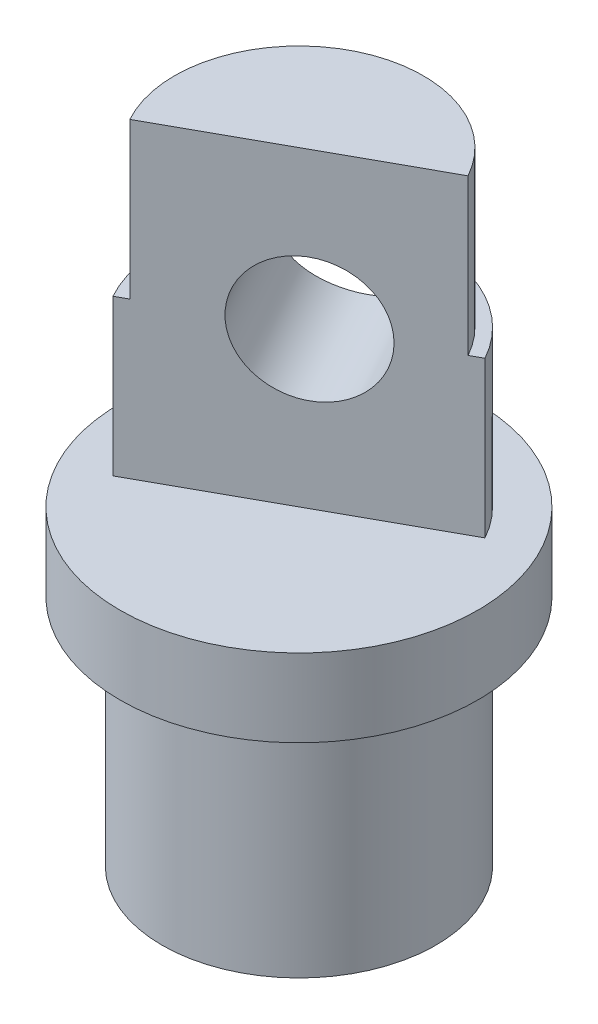
SolidWorks part; units mm, degrees
note: The reader was unsure of these and kept them because the rebuilt part matched: shared geometry of "Sketch1<4>", "Sketch1<6>", "Sketch1<7>", "Sketch1<8>", "Sketch1<10>".
ref_plane "Front Plane" through (0, 0, 0) normal (0, 0, 1) x (1, 0, 0)
ref_plane "Top Plane" through (0, 0, 0) normal (0, 1, 0) x (1, 0, 0)
ref_plane "Right Plane" through (0, 0, 0) normal (1, 0, 0) x (0, 0, -1)
sketch "Sketch1" plane through (0, 0, 0) normal (0, 1, 0) x (1, 0, 0)
  line L0 (-7.005, -3.8639) -> (7.005, 3.8639)
  line L1 (7.005, 3.8639) -> (7.7055, 4.2502)
  line L2 (7.7055, 4.2502) -> (-10.0697, -5.5543)
  circle A0 centre (0, 0) radius 11.5
  circle A1 centre (0, 0) radius 8.8
  circle A2 centre (0, 0) radius 8
  dimension "D1" = 23
  dimension "D2" = 17.6
  dimension "D3" = 16
extrude "Boss-Extrude1" add sketch "Sketch1" along normal blind 10 contours A1 A2
extrude "Boss-Extrude3" add sketch "Sketch1<4>" against normal blind 5 contours A0 A1 | A1 A2 | L0 A2 | L0 A2
sketch "Sketch1<4>" plane through (0, 0, 0) normal (0, 1, 0) x (1, 0, 0) same geometry as "Sketch1"
extrude "Boss-Extrude4" add sketch "Sketch1<6>" against normal blind 5
sketch "Sketch1<6>" plane through (0, 0, 0) normal (0, 1, 0) x (1, 0, 0) same geometry as "Sketch1"
extrude "Boss-Extrude5" add sketch "Sketch1<7>" along normal blind 20 contours L0 A2
sketch "Sketch1<7>" plane through (0, 0, 0) normal (0, 1, 0) x (1, 0, 0) same geometry as "Sketch1"
extrude "Boss-Extrude6" add sketch "Sketch1<8>" against normal blind 5
sketch "Sketch1<8>" plane through (0, 0, 0) normal (0, 1, 0) x (1, 0, 0) same geometry as "Sketch1"
extrude "Boss-Extrude8" add sketch "Sketch1<10>" against normal blind 20
sketch "Sketch1<10>" plane through (0, 0, 0) normal (0, 1, 0) x (1, 0, 0) same geometry as "Sketch1"
sketch "Sketch8" plane through (0, 0, 0) normal (0.483, 0, 0.8756) x (0.8756, 0, -0.483)
  line L0 (8, 20) -> (8, 10) construction
  line L1 (-8, 20) -> (-8, 10) construction
  line L2 (8, 20) -> (-8, 20) construction
  line L3 (-8, 0) -> (8, 0) construction
  circle A0 centre (0.5, 10) radius 4
  dimension "D1" = 8
  dimension "D2" = 7.5
  dimension "D3" = 8.5
  dimension "D5" = 10
  dimension "D4" = 10
extrude "Cut-Extrude2" cut sketch "Sketch8" against normal blind 20 contours A0
